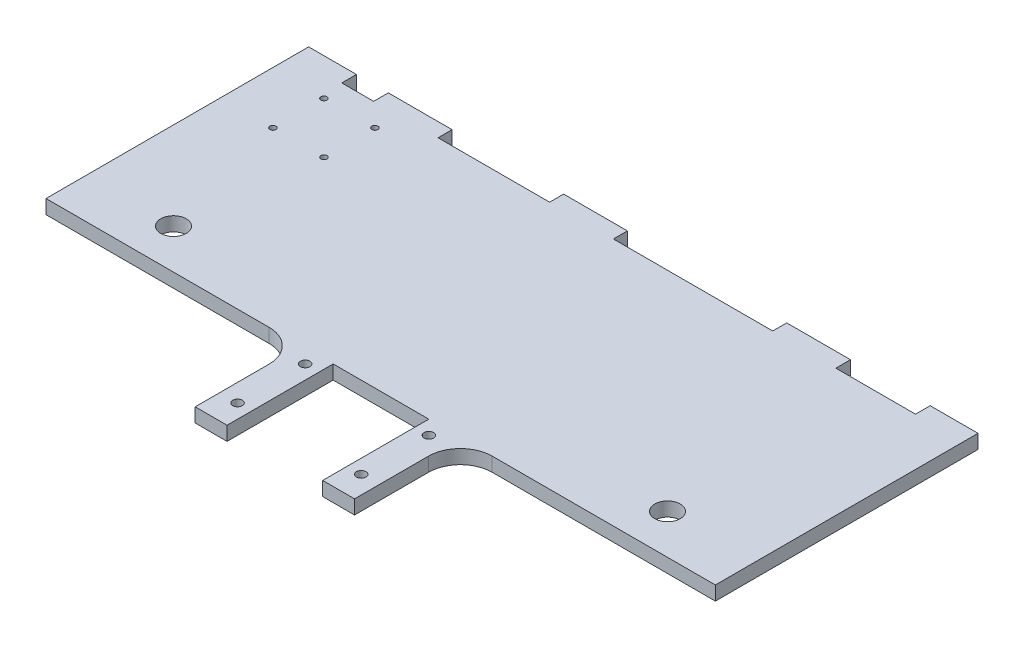
SolidWorks part; units mm, degrees
ref_plane "Front Plane" through (0, 0, 0) normal (0, 0, 1) x (1, 0, 0)
ref_plane "Top Plane" through (0, 0, 0) normal (0, 1, 0) x (1, 0, 0)
ref_plane "Right Plane" through (0, 0, 0) normal (1, 0, 0) x (0, 0, -1)
sketch "Sketch1" plane through (0, 0, 0) normal (0, 1, 0) x (1, 0, 0)
  line L0 (12.7, 98.806) -> (279.4, 98.806) construction
  line L3 (12.7, 104.648) -> (31.75, 104.648)
  line L5 (31.75, 104.648) -> (31.75, 98.806)
  line L6 (31.75, 98.806) -> (44.45, 98.806)
  line L7 (12.7, 0) -> (279.4, 0) construction
  line L8 (44.45, 98.806) -> (44.45, 104.648)
  line L10 (114.3, -42.164) -> (127, -42.164)
  line L12 (146.05, 0.1228) -> (165.1, 0.1228)
  line L13 (165.1, 0.1228) -> (165.1, -42.164)
  line L14 (146.05, 0.1228) -> (127, 0.1228)
  line L15 (127, 0.1228) -> (127, -42.164)
  line L16 (165.1, -42.164) -> (177.8, -42.164)
  line L17 (12.7, 0) -> (101.6, 0)
  line L18 (114.3, -12.7) -> (114.3, -42.164)
  line L19 (279.4, 0) -> (190.5, 0)
  line L20 (177.8, -12.7) -> (177.8, -42.164)
  line L27 (114.3, 104.648) -> (139.7, 104.648)
  line L28 (203.2, 104.648) -> (228.6, 104.648)
  line L29 (69.85, 104.648) -> (69.85, 99.06)
  line L30 (69.85, 99.06) -> (114.3, 99.06)
  line L31 (114.3, 99.06) -> (114.3, 104.648)
  line L32 (139.7, 104.648) -> (139.7, 99.06)
  line L33 (139.7, 99.06) -> (203.2, 99.06)
  line L34 (203.2, 99.06) -> (203.2, 104.648)
  line L35 (228.6, 104.648) -> (228.6, 98.806)
  line L36 (228.6, 98.806) -> (260.35, 98.806)
  line L37 (260.35, 98.806) -> (260.35, 104.648)
  line L38 (44.45, 104.648) -> (69.85, 104.648)
  line L39 (260.35, 104.648) -> (279.4, 104.648)
  line L40 (279.4, 104.648) -> (279.4, 0)
  line L41 (12.7, 104.648) -> (12.7, 0)
  arc A0 (190.5, 0) -> (177.8, -12.7) centre (190.5, -12.7) ccw
  arc A1 (114.3, -12.7) -> (101.6, 0) centre (101.6, -12.7) ccw
  point P0 (0, 0)
  point P10 (0, -41.181)
  point P27 (95.25, 0)
  dimension "D6" = 12.7
  dimension "D3" = 5.842
  dimension "D4" = 98.806
  dimension "D5" = 19.05
  dimension "D7" = 12.7
  dimension "D8" = 19.05
  dimension "D9" = 44.45
  dimension "D10" = 25.4
  dimension "D11" = 5.588
  dimension "D12" = 25.4
  dimension "D13" = 29.464
  dimension "D14" = 42.2868
  dimension "D15" = 12.7
  dimension "D16" = 31.75
  dimension "D17" = 25.4
  dimension "D18" = 19.05
  dimension "D20" = 266.7
extrude "Boss-Extrude1" add sketch "Sketch1" along normal blind 5.588
sketch "Sketch2" plane through (0, 0, 0) normal (0, -1, 0) x (1, 0, 0)
  point P0 (121.412, 32.3976)
  point P1 (170.688, 32.3976)
  point P3 (121.412, 5.4568)
  point P5 (170.688, 5.4568)
hole_wizard "#6 Clearance Hole1" positions "Sketch3" profile "Sketch4" hole size "#6" standard "ANSI Inch" end condition through all
sketch "Sketch3" plane through (0, 0, 0) normal (0, -1, 0) x (-1, 0, 0)
  point P0 (-121.412, -32.3976)
  point P3 (-170.688, -32.3976)
  point P6 (-170.688, -5.4568)
  point P9 (-121.412, -5.4568)
sketch "Sketch4" plane through (121.412, 0, 32.3976) normal (1, 0, 0) x (0, 0, -1)
  line L0 (0, 0) -> (0, 5.588)
  line L1 (0, 5.588) -> (1.8986, 5.588)
  line L2 (1.8986, 5.588) -> (1.8986, 0)
  line L5 (1.8986, 0) -> (0, 0)
  line L11 (0, -6.35) -> (0, 107.95) construction
  dimension "Thru Hole Dia." = 3.7973
  dimension "Thru Hole Depth" = 5.588
sketch "Sketch5" plane through (0, 5.588, 0) normal (0, 1, 0) x (1, 0, 0)
  point P0 (33.528, 89.916)
  point P1 (53.848, 89.916)
  point P3 (53.848, 69.596)
  point P5 (33.528, 69.596)
hole_wizard "M2 Clearance Hole1" positions "Sketch6" profile "Sketch7" hole size "M2" standard "ANSI Metric" end condition through all
sketch "Sketch6" plane through (0, 5.588, 0) normal (0, 1, 0) x (1, 0, 0)
  point P0 (33.528, 89.916)
  point P3 (53.848, 89.916)
  point P6 (53.848, 69.596)
  point P9 (33.528, 69.596)
sketch "Sketch7" plane through (33.528, 5.588, -89.916) normal (1, 0, 0) x (0, 0, 1)
  line L0 (0, 0) -> (0, 5.588)
  line L1 (0, 5.588) -> (1.2, 5.588)
  line L2 (1.2, 5.588) -> (1.2, 0)
  line L5 (1.2, 0) -> (0, 0)
  line L11 (0, -6.35) -> (0, 107.95) construction
  dimension "Thru Hole Dia." = 2.4
  dimension "Thru Hole Depth" = 5.588
sketch "Sketch8" plane through (0, 5.588, 0) normal (0, 1, 0) x (1, 0, 0)
  line L0 (12.7, 5.7108) -> (279.4, 5.7108) construction
  line L3 (127, -42.164) -> (127, 0.1228) construction
  line L4 (165.1, 0.1228) -> (165.1, -42.164) construction
  circle A0 centre (47.625, 15.8708) radius 5.08
  circle A1 centre (244.475, 15.8708) radius 5.08
  dimension "D1" = 10.16
  dimension "D3" = 10.16
  dimension "D2" = 79.375
  dimension "D4" = 10.16
  dimension "D5" = 79.375
extrude "Cut-Extrude1" cut sketch "Sketch8" against normal up to next
